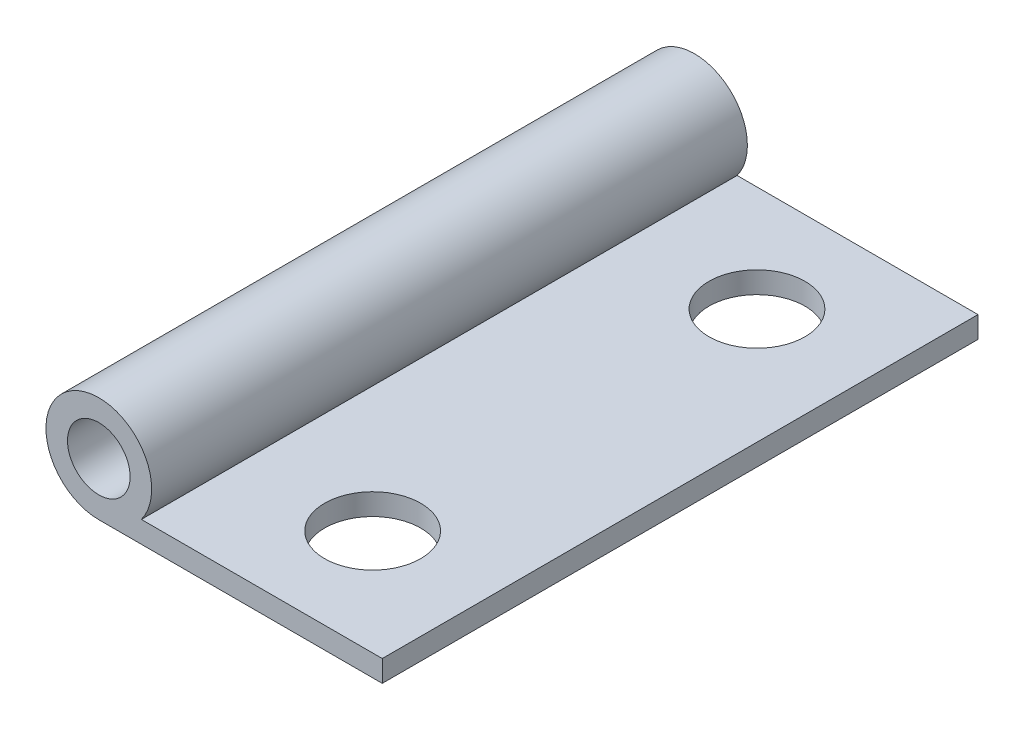
SolidWorks part; units mm, degrees
ref_plane "Front Plane" through (0, 0, 0) normal (0, 0, 1) x (1, 0, 0)
ref_plane "Top Plane" through (0, 0, 0) normal (0, 1, 0) x (1, 0, 0)
ref_plane "Right Plane" through (0, 0, 0) normal (1, 0, 0) x (0, 0, -1)
sketch "Sketch1" plane through (0, 0, 0) normal (0, 1, 0) x (1, 0, 0)
  line L0 (0, 10) -> (0, -10) construction
  line L1 (-6, 15.5) -> (6, 15.5)
  line L2 (-6, 15.5) -> (-6, -15.5)
  line L3 (-6, -15.5) -> (6, -15.5)
  line L4 (6, 15.5) -> (6, -15.5)
  line L5 (-6, 15.5) -> (6, -15.5) construction
  line L6 (-6, -15.5) -> (6, 15.5) construction
  circle A0 centre (0, 10) radius 2.5
  circle A1 centre (0, -10) radius 2.5
  point P0 (0, 0)
  point P10 (0, 0)
  point P11 (0, -9.8068)
  dimension "D3" = 5
  dimension "D4" = 5
  dimension "D1" = 31
  dimension "D2" = 12
  dimension "D5" = 5.5
extrude "Boss-Extrude1" add sketch "Sketch1" along normal blind 1.12
sketch "Sketch2" plane through (0, 0, 15.5) normal (0, 0, 1) x (1, 0, 0)
  line L0 (-6, 0) -> (6, 0) construction
  line L1 (-6, 1.12) -> (-6, 0) construction
  line L3 (-6, 1.12) -> (-6.5351, 1.12)
  line L4 (-6, 1.12) -> (-6, 0)
  line L5 (-6, 0) -> (-8.75, 0)
  arc A0 (-6.5351, 1.12) -> (-8.75, 0) centre (-8.75, 2.75) ccw
  circle A1 centre (-8.75, 2.75) radius 1.63
  dimension "D1" = 2.75
  dimension "D2" = 3.26
extrude "Boss-Extrude2" add sketch "Sketch2" against normal up to surface (31 mm away) up to face at (0, 0.56, -15.5)
